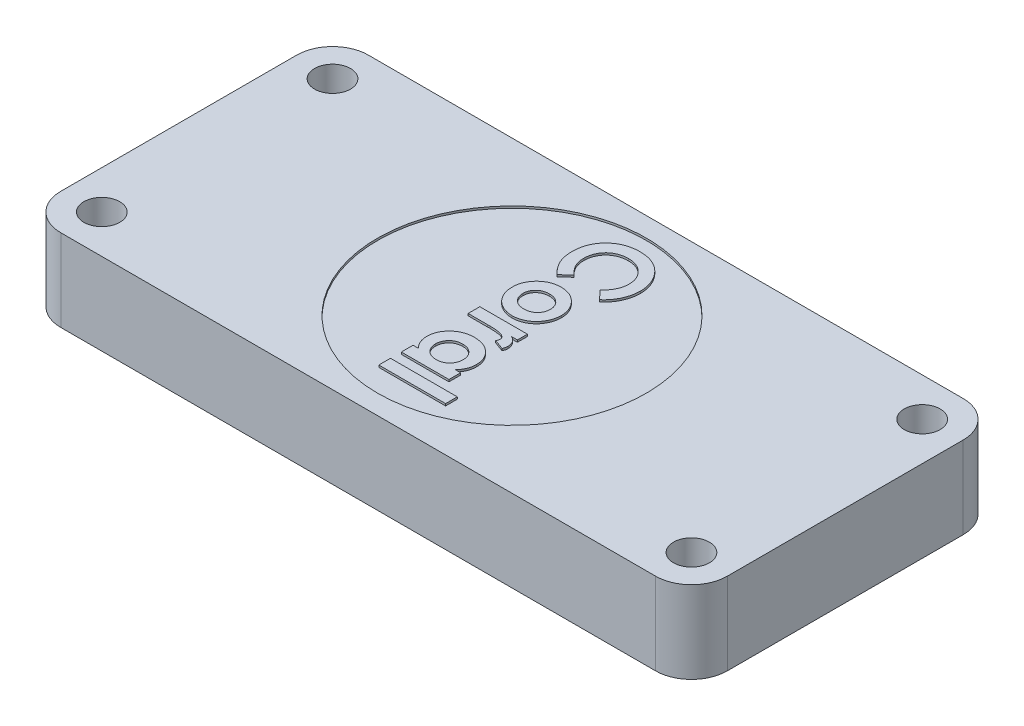
SolidWorks part; units mm, degrees
ref_plane "Front" through (0, 0, 0) normal (0, 0, 1) x (1, 0, 0)
ref_plane "Top" through (0, 0, 0) normal (0, 1, 0) x (1, 0, 0)
ref_plane "Right" through (0, 0, 0) normal (1, 0, 0) x (0, 0, -1)
sketch "Sketch1" plane through (0, 0, 0) normal (0, 1, 0) x (1, 0, 0)
  line L0 (0, 0) -> (0, 15) construction
  line L1 (-32.5, -15) -> (32.5, -15)
  line L2 (-32.5, -15) -> (-32.5, 15)
  line L3 (-32.5, 15) -> (32.5, 15)
  line L4 (32.5, -15) -> (32.5, 15)
  line L5 (-32.5, -15) -> (32.5, 15) construction
  line L6 (-32.5, 15) -> (32.5, -15) construction
  line L7 (0, 15) -> (0, 0) construction
  line L8 (0, 0) -> (-32.5, 0) construction
  circle A0 centre (-28.75, 11.25) radius 1.75
  circle A1 centre (-28.75, -11.25) radius 1.75
  circle A2 centre (28.75, 11.25) radius 1.75
  circle A3 centre (28.75, -11.25) radius 1.75
  point P0 (0, 0)
  dimension "D3" = 3.5
  dimension "D1" = 30
  dimension "D2" = 65
  dimension "D4" = 57.5
  dimension "D5" = 22.5
extrude "Boss-Extrude1" add sketch "Sketch1" along normal blind 8
fillet "Fillet1" radius 3.5 4 edges at (-32.5, 4, -15) (32.5, 4, -15) (32.5, 4, 15) (-32.5, 4, 15)
sketch "Sketch2" plane through (0, 8, 0) normal (0, 1, 0) x (1, 0, 0)
  line L0 (2.9244, 5.6173) -> (2.1256, 6.453)
  line L1 (-0.4236, 6.453) -> (-1.2746, 5.6427)
  line L2 (2.3164, -0.8141) -> (2.3164, -1.791)
  line L3 (2.3164, -1.791) -> (1.7452, -1.791)
  line L4 (2.2833, -3.2564) -> (1.3178, -2.9028)
  line L5 (-0.2188, -1.95) -> (-0.4452, -1.9538)
  line L6 (-0.4452, -1.9538) -> (-2.324, -1.9538)
  line L7 (-2.324, -1.9538) -> (-2.324, -0.8141)
  line L8 (-2.324, -0.8141) -> (2.3164, -0.8141)
  line L9 (2.3164, -7.3269) -> (2.3164, -8.4667)
  line L10 (2.3164, -8.4667) -> (-2.324, -8.4667)
  line L11 (-2.324, -8.4667) -> (-2.324, -7.3269)
  line L12 (-2.324, -7.3269) -> (-1.8177, -7.3269)
  line L13 (1.7936, -7.3269) -> (2.3164, -7.3269)
  line L14 (4.1888, -9.525) -> (4.1888, -10.6647)
  line L15 (4.1888, -10.6647) -> (-2.324, -10.6647)
  line L16 (-2.324, -10.6647) -> (-2.324, -9.525)
  line L17 (-2.324, -9.525) -> (4.1888, -9.525)
  circle A0 centre (0, 0) radius 13.1037
  spline S0 degree 3 poles (2.1256, 6.453) (2.2705, 6.589) (2.4743, 6.801) (2.6896, 7.1176) (2.8227, 7.354) (2.9232, 7.5992) (3.0218, 7.9346) (3.0494, 8.1965) (3.0491, 8.3713) knots 0 0 0 0 0.272304 0.399525 0.522811 0.642663 0.761023 1 1 1 1
  spline S1 degree 3 poles (3.0491, 8.3713) (3.048, 8.516) (3.0314, 8.731) (2.9635, 9.006) (2.8947, 9.201) (2.8054, 9.3869) (2.6961, 9.564) (2.5674, 9.732) (2.4203, 9.8886) (2.2595, 10.0319) (2.088, 10.1584) (1.9061, 10.2644) (1.7156, 10.3515) (1.5158, 10.4192) (1.2329, 10.4849) (1.0122, 10.5003) (0.8637, 10.5019) knots 0 0 0 0 0.127707 0.188882 0.249158 0.309661 0.370225 0.432332 0.495782 0.559304 0.621861 0.683322 0.744523 0.806088 0.868994 1 1 1 1
  spline S2 degree 3 poles (0.8637, 10.5019) (0.7592, 10.5024) (0.6041, 10.4945) (0.4015, 10.4656) (0.2564, 10.4349) (0.1159, 10.3964) (-0.0211, 10.3512) (-0.1527, 10.2946) (-0.2805, 10.2317) (-0.4009, 10.1586) (-0.5157, 10.0798) (-0.6244, 9.9943) (-0.7264, 9.9017) (-0.8203, 9.8005) (-0.9088, 9.6934) (-0.9897, 9.5786) (-1.0651, 9.4586) (-1.1306, 9.3321) (-1.1899, 9.2028) (-1.2381, 9.0685) (-1.2769, 8.9311) (-1.3099, 8.7908) (-1.3375, 8.5969) (-1.3489, 8.4492) (-1.3471, 8.3496) knots 0 0 0 0 0.090639 0.134485 0.177331 0.219265 0.260785 0.302317 0.343436 0.384181 0.424376 0.464181 0.504012 0.543822 0.583802 0.624419 0.665548 0.706675 0.747827 0.788895 0.830219 0.871707 0.913734 1 1 1 1
  spline S3 degree 3 poles (-1.3471, 8.3496) (-1.3465, 8.1829) (-1.3243, 7.9351) (-1.2399, 7.6195) (-1.1666, 7.433) (-1.0942, 7.2869) (-1.0273, 7.1757) (-0.9523, 7.0607) (-0.8666, 6.9438) (-0.7712, 6.8238) (-0.6245, 6.6578) (-0.507, 6.5342) (-0.4236, 6.453) knots 0 0 0 0 0.22997 0.340704 0.449355 0.505557 0.565303 0.628205 0.694729 0.765019 0.83958 1 1 1 1
  spline S4 degree 3 poles (-1.2746, 5.6427) (-1.3819, 5.7538) (-1.5392, 5.9173) (-1.7263, 6.1461) (-1.8527, 6.3093) (-1.965, 6.4709) (-2.0633, 6.631) (-2.15, 6.7876) (-2.2236, 6.9441) (-2.2861, 7.1014) (-2.34, 7.2632) (-2.3855, 7.4301) (-2.4223, 7.603) (-2.4517, 7.7804) (-2.4788, 8.028) (-2.4876, 8.2167) (-2.4868, 8.3446) knots 0 0 0 0 0.151816 0.22254 0.290278 0.354641 0.415798 0.474709 0.530426 0.58558 0.640906 0.697901 0.75542 0.814521 0.874462 1 1 1 1
  spline S5 degree 3 poles (-2.4868, 8.3446) (-2.4854, 8.5761) (-2.4608, 8.9187) (-2.3607, 9.3569) (-2.257, 9.6633) (-2.1244, 9.9534) (-1.9619, 10.2272) (-1.7698, 10.4841) (-1.5505, 10.7221) (-1.3083, 10.9374) (-1.0482, 11.1277) (-0.769, 11.2851) (-0.4748, 11.4158) (-0.1642, 11.518) (0.2801, 11.6161) (0.6266, 11.6421) (0.8612, 11.6417) knots 0 0 0 0 0.131837 0.194461 0.255346 0.315588 0.375627 0.436138 0.497779 0.55947 0.620278 0.680788 0.741492 0.803215 0.866493 1 1 1 1
  spline S6 degree 3 poles (0.8612, 11.6417) (1.016, 11.643) (1.2445, 11.6276) (1.5441, 11.5863) (1.7582, 11.5382) (1.9672, 11.4801) (2.1687, 11.4079) (2.3634, 11.3217) (2.5515, 11.2241) (2.7319, 11.1138) (2.903, 10.9906) (3.0661, 10.8576) (3.2191, 10.7117) (3.3632, 10.5549) (3.4978, 10.3867) (3.6246, 10.2079) (3.7406, 10.0181) (3.8455, 9.821) (3.938, 9.6191) (4.0153, 9.4128) (4.0795, 9.2031) (4.1273, 8.989) (4.1761, 8.698) (4.1872, 8.4754) (4.1888, 8.3267) knots 0 0 0 0 0.088512 0.130926 0.172904 0.214 0.254985 0.295291 0.335772 0.376181 0.416178 0.45635 0.496512 0.537041 0.578119 0.619725 0.662422 0.705299 0.74743 0.789433 0.831267 0.872825 0.91487 1 1 1 1
  spline S7 degree 3 poles (4.1888, 8.3267) (4.1889, 8.1993) (4.1786, 8.009) (4.145, 7.7572) (4.1073, 7.5711) (4.0626, 7.3859) (4.0039, 7.2039) (3.9386, 7.0224) (3.8605, 6.8442) (3.7752, 6.669) (3.6785, 6.5009) (3.5763, 6.3371) (3.4625, 6.1813) (3.3412, 6.0305) (3.1681, 5.836) (3.0237, 5.7028) (2.9244, 5.6173) knots 0 0 0 0 0.123904 0.185067 0.24684 0.308435 0.370241 0.432587 0.495925 0.559351 0.621943 0.684393 0.746986 0.809441 0.872508 1 1 1 1
  spline S8 degree 3 poles (2.3978, 2.4296) (2.3978, 2.3229) (2.3881, 2.1632) (2.3533, 1.9539) (2.3199, 1.7996) (2.2731, 1.6486) (2.217, 1.5002) (2.1526, 1.3529) (2.0759, 1.2105) (1.9927, 1.072) (1.9009, 0.9406) (1.8013, 0.8175) (1.6962, 0.7004) (1.5809, 0.5948) (1.461, 0.4938) (1.3323, 0.4031) (1.1979, 0.3191) (1.0585, 0.2442) (0.9151, 0.1793) (0.7698, 0.1229) (0.6207, 0.0788) (0.4697, 0.0423) (0.2627, 0.0111) (0.1055, -0.0006) (0, 0) knots 0 0 0 0 0.084364 0.126142 0.167706 0.209066 0.250973 0.293148 0.336041 0.378761 0.420893 0.462622 0.503914 0.545188 0.586138 0.627722 0.669585 0.711432 0.752691 0.793971 0.834592 0.875577 0.91664 1 1 1 1
  spline S9 degree 3 poles (0, 0) (-0.1062, 0.0001) (-0.2651, 0.0096) (-0.4732, 0.0445) (-0.6266, 0.078) (-0.7761, 0.1246) (-0.924, 0.1791) (-1.0683, 0.2459) (-1.2104, 0.3198) (-1.3463, 0.4044) (-1.4763, 0.4951) (-1.597, 0.5956) (-1.7122, 0.7004) (-1.818, 0.8144) (-1.9161, 0.9359) (-2.0076, 1.0638) (-2.0905, 1.1989) (-2.1634, 1.3397) (-2.2291, 1.4836) (-2.2838, 1.6316) (-2.3284, 1.7833) (-2.3629, 1.9389) (-2.3946, 2.1525) (-2.406, 2.3152) (-2.4054, 2.4245) knots 0 0 0 0 0.083839 0.125192 0.166335 0.207602 0.24867 0.290582 0.332926 0.374978 0.416741 0.457857 0.498809 0.539516 0.58042 0.62191 0.663502 0.705394 0.746864 0.788245 0.829736 0.871532 0.913825 1 1 1 1
  spline S10 degree 3 poles (-2.4054, 2.4245) (-2.4038, 2.5833) (-2.3859, 2.8198) (-2.3114, 3.1232) (-2.2347, 3.3393) (-2.1364, 3.5468) (-2.0148, 3.744) (-1.8722, 3.9327) (-1.7098, 4.1098) (-1.5317, 4.272) (-1.3416, 4.4137) (-1.1423, 4.534) (-0.9336, 4.6329) (-0.7152, 4.7091) (-0.408, 4.7838) (-0.1685, 4.8017) (-0.0076, 4.8032) knots 0 0 0 0 0.126884 0.188201 0.248894 0.309599 0.371125 0.433466 0.498143 0.562593 0.625474 0.687114 0.748125 0.809457 0.871431 1 1 1 1
  spline S11 degree 3 poles (-0.0076, 4.8032) (0.1642, 4.8029) (0.4188, 4.7797) (0.7449, 4.6972) (0.9747, 4.6102) (1.1935, 4.4988) (1.474, 4.3155) (1.6602, 4.1416) (1.7758, 4.0158) knots 0 0 0 0 0.256474 0.379237 0.500978 0.622367 0.744855 1 1 1 1
  spline S12 degree 3 poles (1.7758, 4.0158) (1.8776, 3.9052) (2.0118, 3.7266) (2.1573, 3.4712) (2.2462, 3.2757) (2.313, 3.0729) (2.3788, 2.7923) (2.3972, 2.5753) (2.3978, 2.4296) knots 0 0 0 0 0.258464 0.38258 0.504991 0.627227 0.749297 1 1 1 1
  spline S13 degree 3 poles (1.3395, 2.4041) (1.3371, 2.4907) (1.3309, 2.6202) (1.2878, 2.784) (1.2475, 2.9004) (1.1934, 3.0102) (1.1302, 3.1164) (1.0511, 3.2136) (0.9644, 3.3063) (0.868, 3.3905) (0.7631, 3.4622) (0.6535, 3.5263) (0.5353, 3.575) (0.4117, 3.6151) (0.2342, 3.6523) (0.0964, 3.665) (0.0025, 3.6635) knots 0 0 0 0 0.126803 0.187423 0.246518 0.306285 0.365703 0.426477 0.488622 0.550895 0.612679 0.673914 0.735734 0.798735 0.86329 1 1 1 1
  spline S14 degree 3 poles (0.0025, 3.6635) (-0.0936, 3.6638) (-0.2352, 3.6543) (-0.4167, 3.6162) (-0.5427, 3.5767) (-0.6622, 3.5269) (-0.7745, 3.4659) (-0.879, 3.3929) (-0.9756, 3.3101) (-1.0633, 3.2195) (-1.1386, 3.1202) (-1.2039, 3.0164) (-1.2564, 2.9057) (-1.297, 2.7896) (-1.3375, 2.6245) (-1.3454, 2.4951) (-1.3471, 2.408) knots 0 0 0 0 0.139456 0.204809 0.268587 0.330587 0.392213 0.45361 0.515092 0.576402 0.636039 0.695407 0.753981 0.813285 0.873377 1 1 1 1
  spline S15 degree 3 poles (-1.3471, 2.408) (-1.3468, 2.3206) (-1.3354, 2.1912) (-1.296, 2.0254) (-1.2551, 1.9084) (-1.2015, 1.7976) (-1.1358, 1.6926) (-1.0595, 1.5926) (-0.9702, 1.5008) (-0.8733, 1.4157) (-0.7682, 1.3412) (-0.6558, 1.2789) (-0.5369, 1.2278) (-0.4116, 1.1882) (-0.2321, 1.1507) (-0.0925, 1.1381) (0.0025, 1.1397) knots 0 0 0 0 0.126397 0.186939 0.246099 0.305348 0.364572 0.424924 0.486952 0.54955 0.611149 0.672922 0.73501 0.798049 0.862643 1 1 1 1
  spline S16 degree 3 poles (0.0025, 1.1397) (0.0974, 1.1394) (0.2373, 1.149) (0.4164, 1.1867) (0.5405, 1.2268) (0.6584, 1.2763) (0.7695, 1.3374) (0.8732, 1.4107) (0.969, 1.4939) (1.0555, 1.5859) (1.1326, 1.6834) (1.1963, 1.7888) (1.2489, 1.9001) (1.2893, 2.0174) (1.3301, 2.1846) (1.3376, 2.3158) (1.3395, 2.4041) knots 0 0 0 0 0.13784 0.202698 0.265406 0.326938 0.388125 0.449117 0.511101 0.572086 0.632197 0.691339 0.750564 0.810546 0.871335 1 1 1 1
  spline S17 degree 3 poles (1.7452, -1.791) (1.8452, -1.8426) (1.9878, -1.9304) (2.1405, -2.0859) (2.234, -2.2106) (2.3068, -2.3463) (2.3767, -2.5379) (2.3989, -2.6902) (2.3978, -2.7921) knots 0 0 0 0 0.268422 0.393205 0.51643 0.637793 0.758061 1 1 1 1
  spline S18 degree 3 poles (2.3978, -2.7921) (2.3961, -2.8681) (2.3787, -3.0293) (2.3177, -3.1796) (2.2833, -3.2564) knots 0 0 0 0 0.474168 1 1 1 1
  spline S19 degree 3 poles (1.3178, -2.9028) (1.3463, -2.8435) (1.3974, -2.7389) (1.4203, -2.6244) (1.4209, -2.5746) knots 0 0 0 0 0.570645 1 1 1 1
  spline S20 degree 3 poles (1.4209, -2.5746) (1.4208, -2.5321) (1.4114, -2.4669) (1.3745, -2.3878) (1.3393, -2.3292) (1.2903, -2.2761) (1.2335, -2.223) (1.1635, -2.1762) (1.0855, -2.1268) (0.99, -2.0848) (0.8761, -2.0487) (0.7423, -2.0166) (0.588, -1.9945) (0.4147, -1.9731) (0.1436, -1.9552) (-0.0699, -1.949) (-0.2188, -1.95) knots 0 0 0 0 0.066912 0.101141 0.136381 0.173598 0.214076 0.25798 0.305417 0.358685 0.420924 0.492691 0.574131 0.665182 0.766513 1 1 1 1
  spline S21 degree 3 poles (-1.8177, -7.3269) (-1.9151, -7.2191) (-2.0487, -7.0529) (-2.1891, -6.8149) (-2.2707, -6.6404) (-2.3308, -6.4618) (-2.39, -6.2134) (-2.4045, -6.0198) (-2.4054, -5.8895) knots 0 0 0 0 0.273944 0.399987 0.519719 0.636176 0.754371 1 1 1 1
  spline S22 degree 3 poles (-2.4054, -5.8895) (-2.407, -5.7426) (-2.3845, -5.5248) (-2.3123, -5.2446) (-2.2371, -5.044) (-2.1394, -4.8514) (-2.022, -4.6653) (-1.8808, -4.4888) (-1.7218, -4.3206) (-1.5469, -4.1665) (-1.3585, -4.0318) (-1.1593, -3.9183) (-0.95, -3.8253) (-0.7307, -3.7522) (-0.4194, -3.6813) (-0.1766, -3.664) (-0.0127, -3.6635) knots 0 0 0 0 0.121092 0.179634 0.238304 0.297437 0.357507 0.419513 0.4836 0.548295 0.611487 0.674313 0.737107 0.80016 0.864737 1 1 1 1
  spline S23 degree 3 poles (-0.0127, -3.6635) (0.156, -3.6648) (0.4061, -3.68) (0.7261, -3.7498) (0.9498, -3.8196) (1.1616, -3.9094) (1.3619, -4.0187) (1.55, -4.1491) (1.7228, -4.2994) (1.8813, -4.4617) (2.0192, -4.6353) (2.1363, -4.8175) (2.232, -5.0085) (2.3058, -5.2083) (2.3791, -5.4885) (2.3979, -5.7077) (2.3978, -5.8552) knots 0 0 0 0 0.139309 0.205474 0.269598 0.332253 0.39483 0.457376 0.520582 0.583374 0.644082 0.70304 0.761664 0.819844 0.878346 1 1 1 1
  spline S24 degree 3 poles (2.3978, -5.8552) (2.3994, -5.9922) (2.3791, -6.1954) (2.3158, -6.458) (2.2493, -6.6462) (2.1652, -6.8286) (2.023, -7.064) (1.8919, -7.2267) (1.7936, -7.3269) knots 0 0 0 0 0.251537 0.373434 0.495667 0.61768 0.742091 1 1 1 1
  spline S25 degree 3 poles (1.3395, -6.0943) (1.3381, -6.0054) (1.3293, -5.8733) (1.2899, -5.7039) (1.2472, -5.5855) (1.1951, -5.472) (1.1299, -5.3652) (1.0527, -5.2641) (0.9656, -5.1694) (0.8698, -5.083) (0.7653, -5.0086) (0.6549, -4.9454) (0.5383, -4.8919) (0.414, -4.8536) (0.2373, -4.8124) (0.0985, -4.8052) (0.0051, -4.8032) knots 0 0 0 0 0.128421 0.189996 0.250359 0.309744 0.369856 0.430537 0.492876 0.555257 0.616197 0.677577 0.738631 0.800922 0.864882 1 1 1 1
  spline S26 degree 3 poles (0.0051, -4.8032) (-0.0893, -4.8049) (-0.229, -4.813) (-0.4081, -4.8527) (-0.5329, -4.8954) (-0.652, -4.9475) (-0.7649, -5.0109) (-0.8694, -5.0888) (-0.9682, -5.1752) (-1.0564, -5.2718) (-1.1348, -5.3735) (-1.2003, -5.4815) (-1.2532, -5.5947) (-1.2964, -5.7128) (-1.3352, -5.8806) (-1.3467, -6.0112) (-1.3471, -6.0994) knots 0 0 0 0 0.135365 0.199461 0.262264 0.323991 0.385461 0.447171 0.510418 0.573171 0.634271 0.693954 0.753723 0.813084 0.873629 1 1 1 1
  spline S27 degree 3 poles (-1.3471, -6.0994) (-1.3456, -6.19) (-1.3371, -6.3242) (-1.2976, -6.4962) (-1.2546, -6.6162) (-1.2029, -6.7312) (-1.1389, -6.8403) (-1.062, -6.9422) (-0.9741, -7.0375) (-0.8775, -7.1247) (-0.7716, -7.2002) (-0.6598, -7.2659) (-0.5394, -7.3176) (-0.4126, -7.3586) (-0.2303, -7.3988) (-0.0875, -7.4066) (0.0089, -7.4083) knots 0 0 0 0 0.128662 0.18979 0.249707 0.309189 0.3685 0.428644 0.489937 0.552121 0.612878 0.67405 0.735729 0.798305 0.862953 1 1 1 1
  spline S28 degree 3 poles (0.0089, -7.4083) (0.1032, -7.4067) (0.2431, -7.3988) (0.4218, -7.3584) (0.5465, -7.3182) (0.664, -7.2656) (0.7731, -7.1998) (0.8775, -7.1252) (0.9715, -7.0369) (1.0588, -6.9422) (1.1334, -6.8388) (1.1977, -6.73) (1.2505, -6.6151) (1.2892, -6.4931) (1.33, -6.3205) (1.3378, -6.1852) (1.3395, -6.0943) knots 0 0 0 0 0.135096 0.199063 0.261548 0.322044 0.382646 0.443385 0.505155 0.566516 0.627254 0.687026 0.74697 0.807539 0.869733 1 1 1 1
  point P2 (-0.4732, 0.0458)
extrude "Cut-Extrude1" cut sketch "Sketch2" against normal blind 0.2 contours A0 L16 L17 L14 L15 S6 S7 L0 S0 S1 S2 S3 L1 S4 S5 S11 S12 S8 S9 S10 S19 S20 L5 L6 L7 L8 L2 L3 S17 S18 L4 S23 S24 L13 L9 L10 L11 L12 S21 S22 | S15 S16 S13 S14 | S27 S28 S25 S26 region at (-12.7331, 8, 0) region at (-0.0031, 8, -2.4021) region at (-0.0016, 8, 6.1069)
